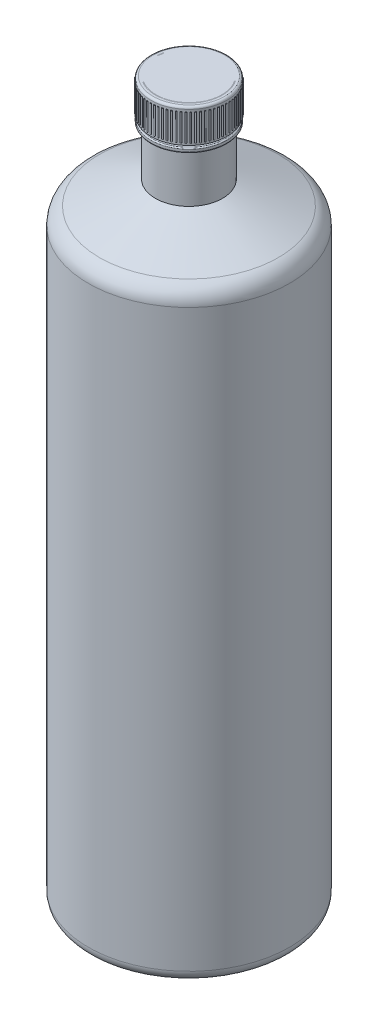
SolidWorks part; units mm, degrees
material "ABS PC"
ref_plane "Front Plane" through (0, 0, 0) normal (0, 0, 1) x (1, 0, 0)
ref_plane "Top Plane" through (0, 0, 0) normal (0, 1, 0) x (1, 0, 0)
ref_plane "Right Plane" through (0, 0, 0) normal (1, 0, 0) x (0, 0, -1)
sketch "Sketch1" plane through (0, 0, 0) normal (0, 0, 1) x (1, 0, 0)
  line L0 (0, 0) -> (0, 95.6985) construction
  line L1 (0, 0) -> (40, 0)
  line L2 (45, 5.011) -> (45, 262.0766)
  line L3 (40, 269.5781) -> (15, 280)
  line L4 (15, 280) -> (15, 320)
  line L5 (15, 320) -> (17, 320) construction
  line L6 (17, 320) -> (17, 305) construction
  arc A0 (40, 0) -> (45, 5.011) centre (40, 5) ccw
  arc A1 (45, 262.0766) -> (40, 269.5781) centre (36.8728, 262.0766) ccw
  point P9 (17, 312.5)
  dimension "D2" = 5
  dimension "D1" = 90
  dimension "D3" = 30
  dimension "D4" = 320
  dimension "D5" = 280
  dimension "D6" = 15
  dimension "D7" = 34
revolve "Revolve-Thin1" add sketch "Sketch1" angle 360 about L0 wall 0.3
sketch "Sketch2" plane through (0, 0, 0) normal (0, 0, 1) x (1, 0, 0)
  line L0 (17, 320) -> (17, 305) construction
  line L1 (15, 320) -> (17, 320) construction
  line L2 (17, 320) -> (17, 305)
  line L3 (0, 320) -> (17, 320)
  line L4 (0, 328.827) -> (0, 295.4651) construction
  line L5 (17, 305) -> (15, 305)
  line L6 (15, 305) -> (15, 318)
  line L7 (15, 318) -> (0, 318)
  line L8 (0, 318) -> (0, 320)
  dimension "D1" = 2
  dimension "D2" = 2
revolve "Revolve1" add sketch "Sketch2" angle 360 about L4
sketch "Sketch3" plane through (0, 305, 0) normal (0, -1, 0) x (1, 0, 0)
  line L0 (0, -49.5) -> (0, 49.5) construction
  circle A0 centre (0, 17) radius 0.3
  circle A1 centre (0, 0) radius 17 construction
  dimension "D1" = 0.6
extrude "Boss-Extrude1" add sketch "Sketch3" against normal blind 12 from offset 1 offset against normal yes
pattern_circular "CirPattern1" count 69 over 360 about axis through (0, 328.827, 0) along (0, 1, 0) of "Boss-Extrude1" reverse direction yes
fillet "Fillet1" radius 1 1 edges at (0, 320, 17)
sketch "Sketch4" plane through (0, 305, 0) normal (0, -1, 0) x (1, 0, 0)
  circle A1 centre (0, 0) radius 17
  circle A2 centre (0, 0) radius 17
  circle A3 centre (0, 0) radius 15.1
  dimension "D1" = 0
extrude "Boss-Extrude2" add sketch "Sketch4" along normal blind 2 from offset 1 separate body
fillet "Fillet2" radius 0.5 2 edges at (0, 304, -17) (0, 302, -17)
delete or keep bodies "Body-Delete/Keep 1" [suppressed] type delete bodies bodies 106 105
sketch "Sketch6" [suppressed] plane through (0, 320, 0) normal (0, 1, 0) x (1, 0, 0)
  circle A0 centre (0, 0) radius 15 construction
  circle A1 centre (0, 0) radius 15
curve "Helix/Spiral1" [suppressed] pitch 3 height 18 turns 6
sketch "Sketch7" [suppressed] plane through (0, 0, 0) normal (1, 0, 0) x (0, 0, -1)
  line L0 (-15, 320) -> (-16.2124, 319.3)
  line L1 (-16.2124, 319.3) -> (-16.2124, 318.7)
  line L2 (-16.2124, 318.7) -> (-15, 318)
  line L3 (-15, 320) -> (-15, 280) construction
  line L4 (-15, 318) -> (-15, 320)
  line L5 (-15, 319) -> (-16.2124, 319) construction
  dimension "D1" = 2
  dimension "D2" = 0.6
  dimension "D3" = 30
sweep "Sweep1" [suppressed] add profiles "Sketch7" path "Helix/Spiral1"
fillet "Fillet3" [suppressed] radius 2.1
fillet "Fillet4" [suppressed] radius 0.25
